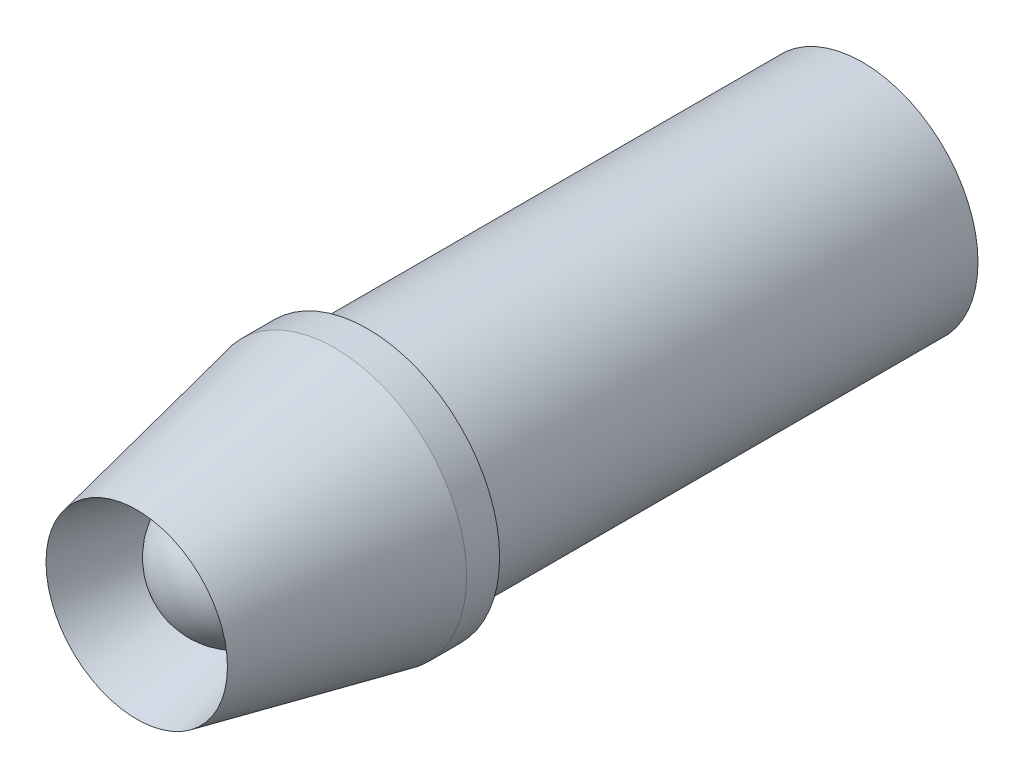
SolidWorks part; units mm, degrees
ref_plane "Plan de face" through (0, 0, 0) normal (0, 0, 1) x (1, 0, 0)
ref_plane "Plan de dessus" through (0, 0, 0) normal (0, 1, 0) x (1, 0, 0)
ref_plane "Plan de droite" through (0, 0, 0) normal (1, 0, 0) x (0, 0, -1)
sketch "Esquisse1" plane through (0, 0, 0) normal (0, 0, 1) x (1, 0, 0)
  circle A0 centre (0, 0) radius 2
  circle A1 centre (0, 0) radius 4
  dimension "D1" = 4
  dimension "D2" = 8
extrude "Boss.-Extru.1" add sketch "Esquisse1" along normal blind 7
chamfer "Chanfrein1" distance 6 distance2 1.25 1 edges at (4, 0, 7) first distance on face at (4, 0, 7)
chamfer "Chanfrein2" distance 0.75 distance2 3 1 edges at (2, 0, 7) first distance on face at (2.75, 0, 7)
ref_plane "Plan2" through (0, 0, 4) normal (0, 0, 1) x (1, 0, 0)
sketch "Esquisse4" plane through (0, 0, 4) normal (0, 0, 1) x (1, 0, 0)
  circle A0 centre (0, 0) radius 2
extrude "Boss.-Extru.2" add sketch "Esquisse4" along normal blind 2 separate body
fillet "Congé1" radius 2 1 edges at (2, 0, 6)
sketch "Esquisse5" plane through (0, 0, 0) normal (0, 0, -1) x (-1, 0, 0)
  circle A0 centre (0, 0) radius 3.5
  dimension "D1" = 7
extrude "Boss.-Extru.3" add sketch "Esquisse5" along normal blind 15
